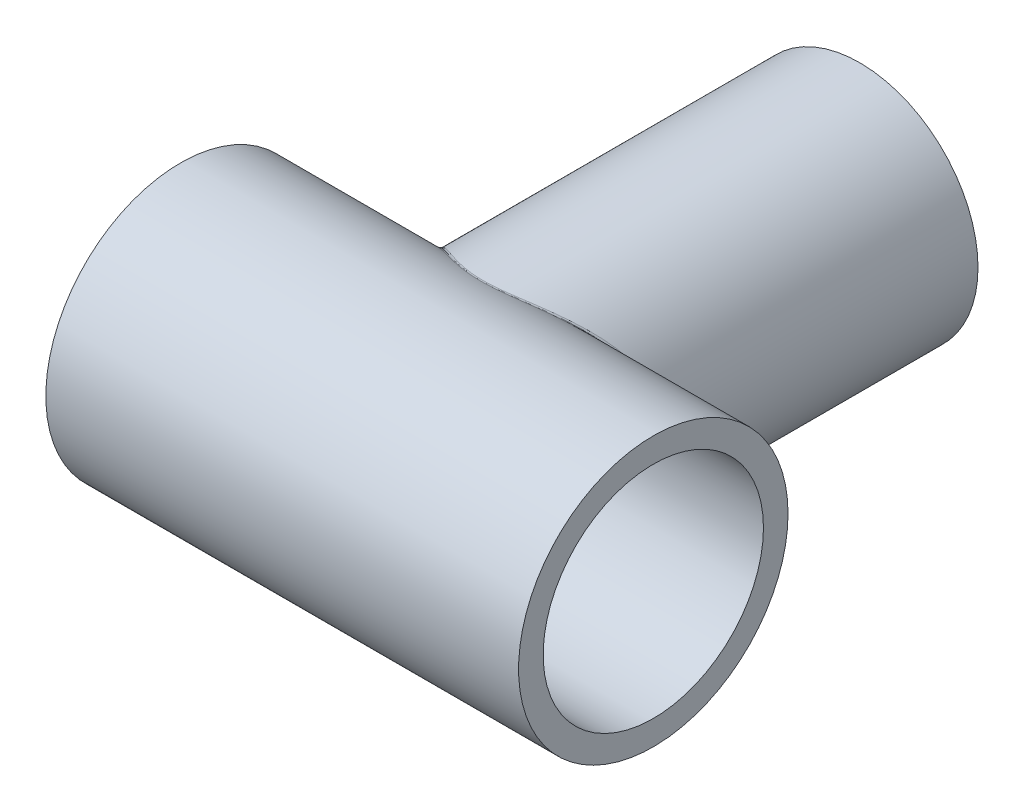
SolidWorks part; units mm, degrees
ref_plane "Front Plane" through (0, 0, 0) normal (0, 0, 1) x (1, 0, 0)
ref_plane "Top Plane" through (0, 0, 0) normal (0, 1, 0) x (1, 0, 0)
ref_plane "Right Plane" through (0, 0, 0) normal (1, 0, 0) x (0, 0, -1)
sketch "Sketch1" plane through (0, 0, 0) normal (0, 0, 1) x (1, 0, 0)
  circle A0 centre (0, 0) radius 25
  circle A1 centre (0, 0) radius 20
  dimension "D1" = 50
  dimension "D2" = 40
extrude "Boss-Extrude1" add sketch "Sketch1" along normal blind 80
sketch "Sketch2" plane through (0, 0, 0) normal (1, 0, 0) x (0, 0, -1)
  circle A0 centre (-93.6839, 0) radius 28.5
  circle A1 centre (-93.6839, 0) radius 23.3
  dimension "D1" = 57
  dimension "D2" = 46.6
extrude "Boss-Extrude2" add sketch "Sketch2" along normal mid plane 100
extrude "Cut-Extrude1" cut sketch "Sketch2<2>" along normal mid plane 60 contours A1
sketch "Sketch2<2>" plane through (0, 0, 0) normal (1, 0, 0) x (0, 0, -1) same geometry as "Sketch2"
fillet "Fillet1" radius 1 1 edges at (-3.6046, 24.7388, 79.5332)
